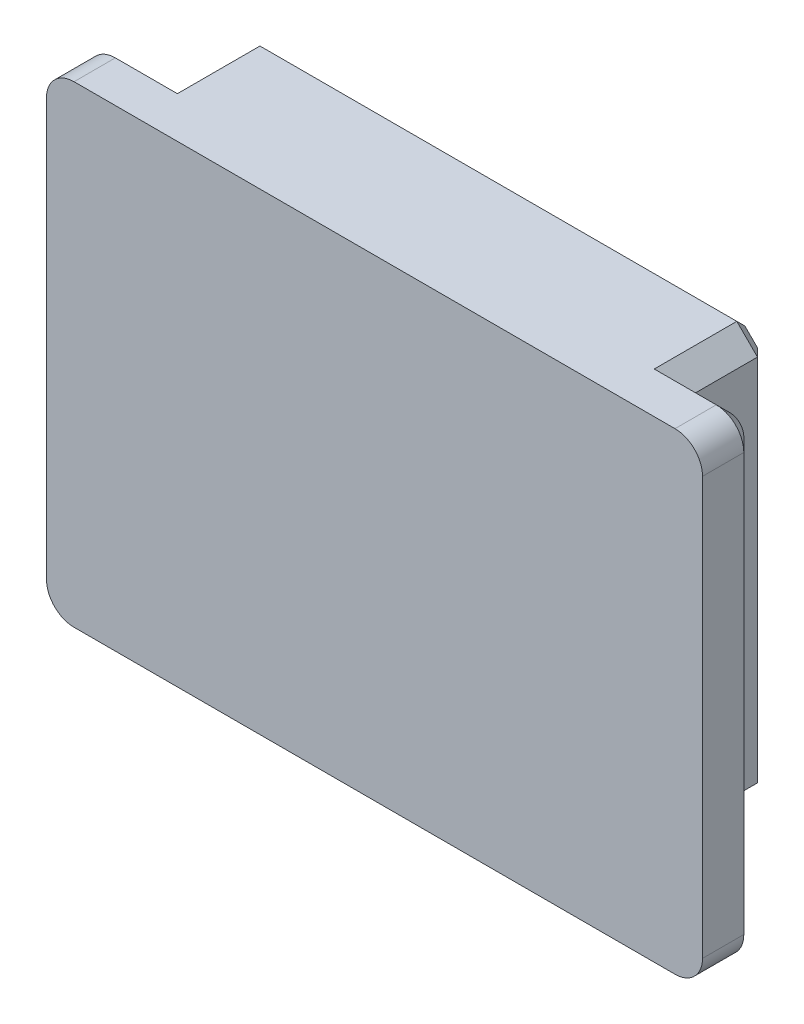
SolidWorks part; units mm, degrees
ref_plane "Front Plane" through (0, 0, 0) normal (0, 0, 1) x (1, 0, 0)
ref_plane "Top Plane" through (0, 0, 0) normal (0, 1, 0) x (1, 0, 0)
ref_plane "Right Plane" through (0, 0, 0) normal (1, 0, 0) x (0, 0, -1)
sketch "Sketch1" plane through (0, 0, 0) normal (0, 0, 1) x (1, 0, 0)
  line L0 (23.8333, 4.537) -> (23.8333, 20.8172) construction
  line L1 (0, 0) -> (47.6667, 0)
  line L2 (0, 0) -> (0, 34.3333)
  line L3 (0, 34.3333) -> (47.6667, 34.3333)
  line L4 (47.6667, 0) -> (47.6667, 34.3333)
  line L5 (5.0076, 34.3333) -> (42.6591, 34.3333)
  line L6 (5.0076, 34.3333) -> (5.0076, 4.537)
  line L7 (5.0076, 4.537) -> (42.6591, 4.537)
  line L8 (42.6591, 34.3333) -> (42.6591, 4.537)
  line L9 (23.8333, 34.3333) -> (23.8333, 20.8172) construction
  point P13 (23.8333, 20.0227)
  dimension "D1" = 34.3333
  dimension "D2" = 47.6667
extrude "Boss-Extrude1" add sketch "Sketch1" along normal blind 4 contours L3 L8 L7 L6 L2 L1 L4 | L8 L3 L6 L7 region at (0.5874, 17.1667, 0) region at (23.8333, 19.4351, 0)
extrude "Boss-Extrude2" add sketch "Sketch1<3>" against normal blind 6 contours L8 L3 L6 L7 region at (23.8333, 19.4351, 0)
sketch "Sketch1<3>" plane through (0, 0, 0) normal (0, 0, 1) x (1, 0, 0) same geometry as "Sketch1"
fillet "Fillet1" radius 2 4 edges at (0, 34.3333, 2) (47.6667, 34.3333, 2) (0, 0, 2) (47.6667, 0, 2)
chamfer "Chamfer1" distance 1.5 angle 45 4 edges at (5.0076, 34.3333, -3) (42.6591, 34.3333, -3) (42.6591, 4.537, -3) (5.0076, 4.537, -3)
chamfer "Chamfer2" distance 1 angle 45 8 edges at (41.9091, 33.5833, -6) (23.8333, 34.3333, -6) (5.7576, 33.5833, -6) (5.0076, 19.4351, -6) (5.7576, 5.287, -6) (42.6591, 19.4351, -6) (41.9091, 5.287, -6) (23.8333, 4.537, -6)
chamfer "Chamfer3" distance 1 angle 45 9 edges at (4.2538, 34.3333, 0) (0.5858, 33.7475, 0) (0, 17.1667, 0) (0.5858, 0.5858, 0) (23.8333, 0, 0) (47.0809, 0.5858, 0) (47.6667, 17.1667, 0) (47.0809, 33.7475, 0) (43.4129, 34.3333, 0)
